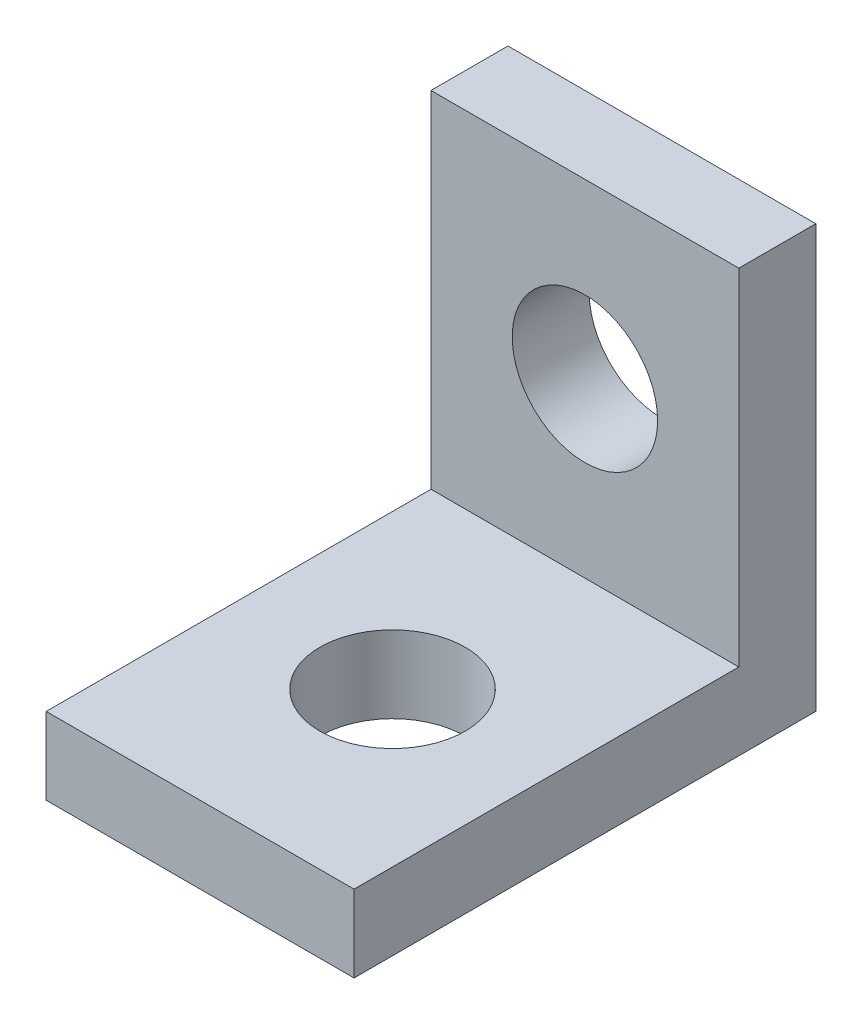
SolidWorks part; units mm, degrees
ref_plane "Front Plane" through (0, 0, 0) normal (0, 0, 1) x (1, 0, 0)
ref_plane "Top Plane" through (0, 0, 0) normal (0, 1, 0) x (1, 0, 0)
ref_plane "Right Plane" through (0, 0, 0) normal (1, 0, 0) x (0, 0, -1)
sketch "Sketch1" plane through (0, 0, 0) normal (0, 1, 0) x (1, 0, 0)
  line L1 (-3.175, 4.7625) -> (3.175, 4.7625)
  line L2 (-3.175, 4.7625) -> (-3.175, -4.7625)
  line L3 (-3.175, -4.7625) -> (3.175, -4.7625)
  line L4 (3.175, 4.7625) -> (3.175, -4.7625)
  line L5 (-3.175, 4.7625) -> (3.175, -4.7625) construction
  line L6 (-3.175, -4.7625) -> (3.175, 4.7625) construction
  point P0 (0, 0)
  dimension "D1" = 6.35
  dimension "D2" = 9.525
extrude "Boss-Extrude1" add sketch "Sketch1" along normal blind 1.5875 contours L1 L4 L3 L2
sketch "Sketch2" plane through (0, 1.5875, 0) normal (0, 1, 0) x (1, 0, 0)
  line L0 (3.175, 4.7625) -> (3.175, -4.7625) construction
  line L1 (-3.175, 4.7625) -> (3.175, 4.7625)
  line L2 (-3.175, 4.7625) -> (-3.175, 3.175)
  line L3 (-3.175, 3.175) -> (3.175, 3.175)
  line L4 (3.175, 4.7625) -> (3.175, 3.175)
  dimension "D1" = 1.5875
extrude "Boss-Extrude2" add sketch "Sketch2" along normal blind 7.1247
hole_wizard "Ø3.0mm Dowel Hole1" positions "Sketch4" profile "Sketch5" hole size "Ø3.0" standard "ANSI Metric" end condition through all
sketch "Sketch4" plane through (0, 1.5875, 0) normal (0, 1, 0) x (1, 0, 0)
  line L0 (-3.175, -4.7625) -> (3.175, 3.175) construction
  point P0 (0, -0.7937)
sketch "Sketch5" plane through (0, 1.5875, 0.7937) normal (1, 0, 0) x (0, 0, 1)
  line L0 (0, 0) -> (0, 1.5875)
  line L1 (0, 1.5875) -> (1.5, 1.5875)
  line L2 (1.5, 1.5875) -> (1.5, 0)
  line L5 (1.5, 0) -> (0, 0)
  line L11 (0, -6.35) -> (0, 107.95) construction
  dimension "Thru Hole Dia." = 3
  dimension "Thru Hole Depth" = 1.5875
hole_wizard "Ø3.0mm Dowel Hole2" positions "Sketch7" profile "Sketch6" hole size "Ø3.0" standard "ANSI Metric"
sketch "Sketch7" plane through (0, 0, -3.175) normal (0, 0, 1) x (1, 0, 0)
  line L0 (-3.175, 1.5875) -> (3.175, 8.7122) construction
  point P0 (0, 5.1498)
sketch "Sketch6" plane through (0, 5.1498, -3.175) normal (1, 0, 0) x (0, -1, 0)
  line L0 (0, 0) -> (0, 7.2513)
  line L1 (0, 7.2513) -> (1.5, 6.35)
  line L2 (1.5, 6.35) -> (1.5, 0)
  line L5 (1.5, 0) -> (0, 0)
  line L10 (0, 7.2513) -> (-1.5, 6.35) construction
  line L11 (0, -6.35) -> (0, 107.95) construction
  dimension "Hole Dia." = 3
  dimension "Hole Depth" = 6.35
  dimension "Drill Angle" = 118
